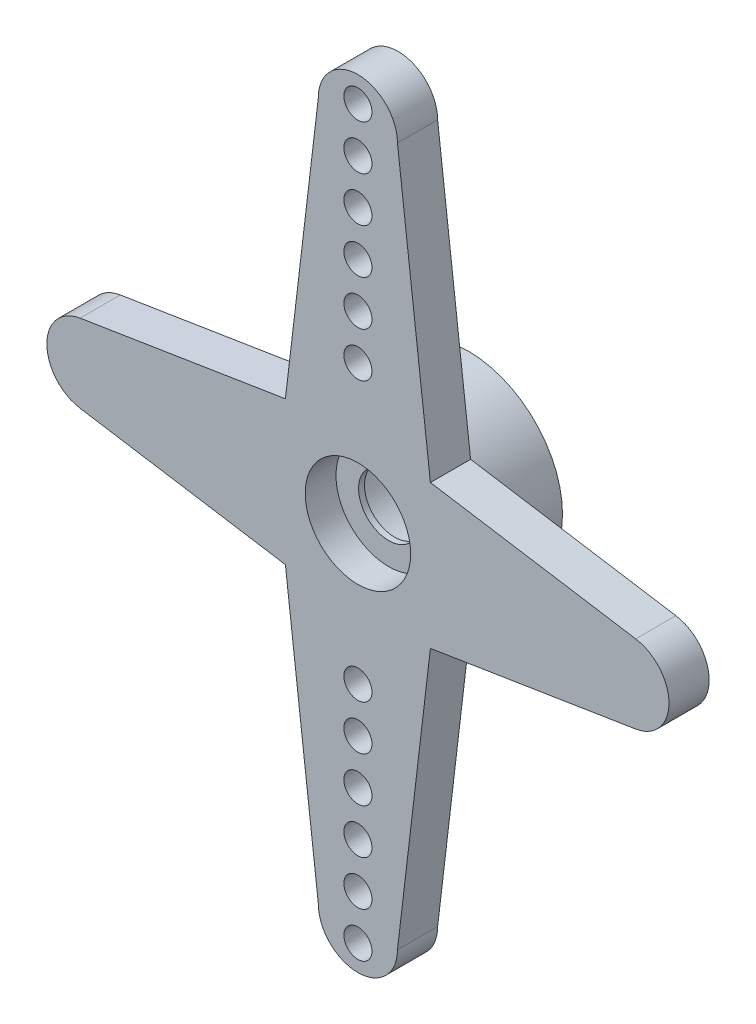
SolidWorks part; units mm, degrees
material "Nylon 6/10"
ref_plane "Front Plane" through (0, 0, 0) normal (0, 0, 1) x (1, 0, 0)
ref_plane "Top Plane" through (0, 0, 0) normal (0, 1, 0) x (1, 0, 0)
ref_plane "Right Plane" through (0, 0, 0) normal (1, 0, 0) x (0, 0, -1)
ref_plane "Plane1" through (0, 0, -7.033) normal (0, 0, 1) x (1, 0, 0)
sketch "Sketch1" plane through (0, 0, -7.033) normal (0, 0, 1) x (1, 0, 0)
  circle A0 centre (-5.5, 0) radius 3.5687
  circle A1 centre (-5.5, 0) radius 2
  dimension "D1" = 7.1374
extrude "Boss-Extrude1" add sketch "Sketch1" along normal blind 4.191
sketch "Sketch5" plane through (0, 0, -4.233) normal (0, 0, 1) x (1, 0, 0)
  circle A0 centre (-5.5, 0) radius 1.143
  circle A1 centre (-5.5, 0) radius 2 construction
  circle A2 centre (-5.5, 0) radius 2
  dimension "D1" = 2.286
extrude "Boss-Extrude2" add sketch "Sketch5" along normal offset from surface (0.2226 mm away) 1.1684 up to face at (-1.9313, 0, -2.842)
sketch "Sketch6" plane through (0, 0, -2.842) normal (0, 0, 1) x (1, 0, 0)
  line L0 (-4, -13.25) -> (-2.6869, -2.196)
  line L1 (-7, -13.25) -> (-8.313, -2.196)
  line L2 (-5.5, 0) -> (-5.5, -13.25) construction
  line L3 (-5.5, -13.7834) -> (-5.5, -12.0816) construction
  arc A0 (-7, -13.25) -> (-4, -13.25) centre (-5.5, -13.25) ccw
  circle A1 centre (-5.5, 0) radius 3.5687 construction
  circle A2 centre (-5.5, 0) radius 3.5687 construction
  circle A3 centre (-5.5, -12.0816) radius 0.5334
  circle A4 centre (-5.5, -13.7834) radius 0.5334
  circle A5 centre (-5.5, -10.3798) radius 0.5334
  circle A6 centre (-5.5, -8.678) radius 0.5334
  circle A7 centre (-5.5, -6.9762) radius 0.5334
  circle A8 centre (-5.5, -5.2744) radius 0.5334
  arc A9 (-2.6869, -2.196) -> (-8.313, -2.196) centre (-5.5, 0) cw
  dimension "D1" = 3
  dimension "D2" = 14.75
  dimension "D4" = 1.0668
  dimension "D3" = 5.6261
  dimension "D6" = 1.7018
  dimension "D5" = 6
extrude "Boss-Extrude3" add sketch "Sketch6" against normal blind 1.524
mirror "Mirror1" about plane through (0, 0, 0) normal (0, 1, 0) of "Boss-Extrude3"
sketch "Sketch7" plane through (0, 0, -2.842) normal (0, 0, 1) x (1, 0, 0)
  line L0 (-16.0365, -1.4812) -> (-7.696, -2.8131)
  line L1 (-16.0365, 1.4812) -> (-7.696, 2.8131)
  line L2 (-5.5, 0) -> (-15.8, 0) construction
  line L3 (-7.696, 2.8131) -> (-7.696, -2.8131) construction
  arc A0 (-16.0365, 1.4812) -> (-16.0365, -1.4812) centre (-15.8, 0) ccw
  circle A1 centre (-5.5, 0) radius 3.5687 construction
  arc A8 (-7.696, -2.8131) -> (-7.696, 2.8131) centre (-5.5, 0) cw
  arc A9 (-2.6869, -2.196) -> (-2.6869, 2.196) centre (-5.5, 0) ccw construction
  dimension "D1" = 3
  dimension "D2" = 11.8
  dimension "D3" = 5.6261
extrude "Boss-Extrude4" add sketch "Sketch7" against normal up to surface (1.524 mm away) up to face at (-5.5, 8.4412, -4.366)
ref_plane "Plane2" through (-1.9313, 0, 0) normal (1, 0, 0) x (0, 0, -1)
ref_plane "Plane3" through (-9.0687, 0, 0) normal (-1, 0, 0) x (0, 0, 1)
ref_plane "Plane4" through (-5.5, 0, 0) normal (-1, 0, 0) x (0, 0, 1)
mirror "Mirror2" about plane through (-5.5, 0, 0) normal (-1, 0, 0) of "Boss-Extrude4"
move or copy body "Body-Move/Copy1" [suppressed] bodies to move or copy 107
